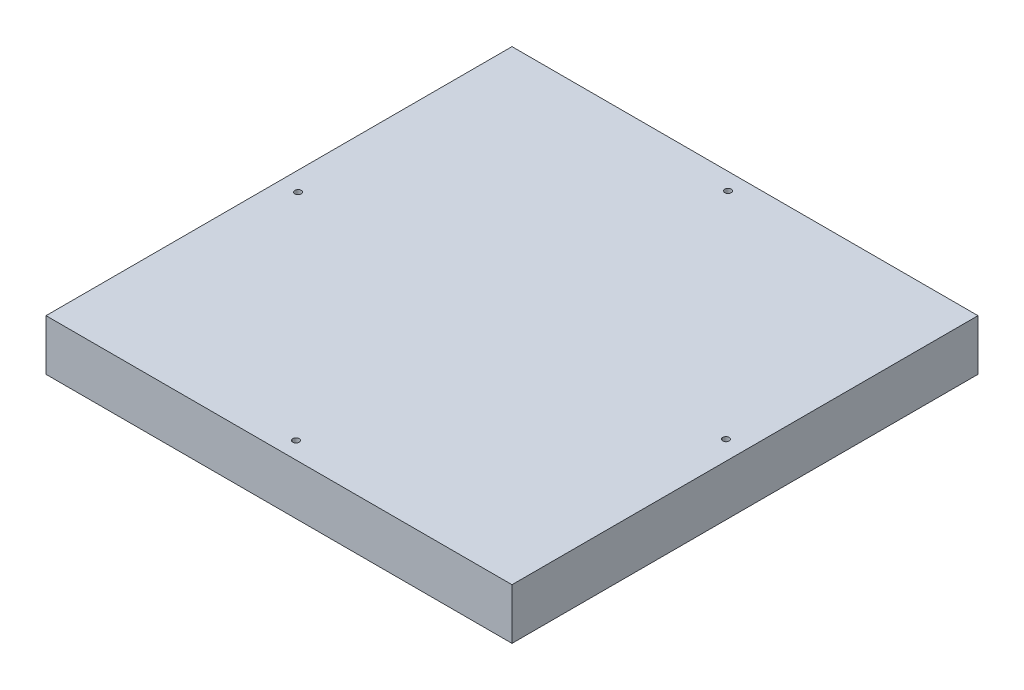
SolidWorks part; units mm, degrees
material "Oak"
ref_plane "Front Plane" through (0, 0, 0) normal (0, 0, 1) x (1, 0, 0)
ref_plane "Top Plane" through (0, 0, 0) normal (0, 1, 0) x (1, 0, 0)
ref_plane "Right Plane" through (0, 0, 0) normal (1, 0, 0) x (0, 0, -1)
sketch "Sketch1" plane through (0, 0, 0) normal (0, 1, 0) x (1, 0, 0)
  line L0 (-101, 0) -> (101, 0) construction
  line L1 (-110, -110) -> (110, -110)
  line L2 (-110, -110) -> (-110, 110)
  line L3 (-110, 110) -> (110, 110)
  line L4 (110, -110) -> (110, 110)
  line L5 (-110, -110) -> (110, 110) construction
  line L6 (-110, 110) -> (110, -110) construction
  line L7 (-101, -102) -> (101, -102) construction
  line L8 (-101, -102) -> (-101, 102) construction
  line L9 (-101, 102) -> (101, 102) construction
  line L10 (101, -102) -> (101, 102) construction
  line L11 (-101, -102) -> (101, 102) construction
  line L12 (-101, 102) -> (101, -102) construction
  line L14 (0, 102) -> (0, -102) construction
  circle A1 centre (-101, 0) radius 1.5
  circle A3 centre (101, 0) radius 1.5
  circle A5 centre (0, -102) radius 1.5
  circle A7 centre (0, 102) radius 1.5
  point P1 (0, 0)
  point P13 (0, 0)
  point P19 (-101, 0)
  point P20 (0, -102)
  dimension "D2" = 204
  dimension "D4" = 3
  dimension "D1" = 220
  dimension "D3" = 202
extrude "Boss-Extrude1" add sketch "Sketch1" along normal blind 24
